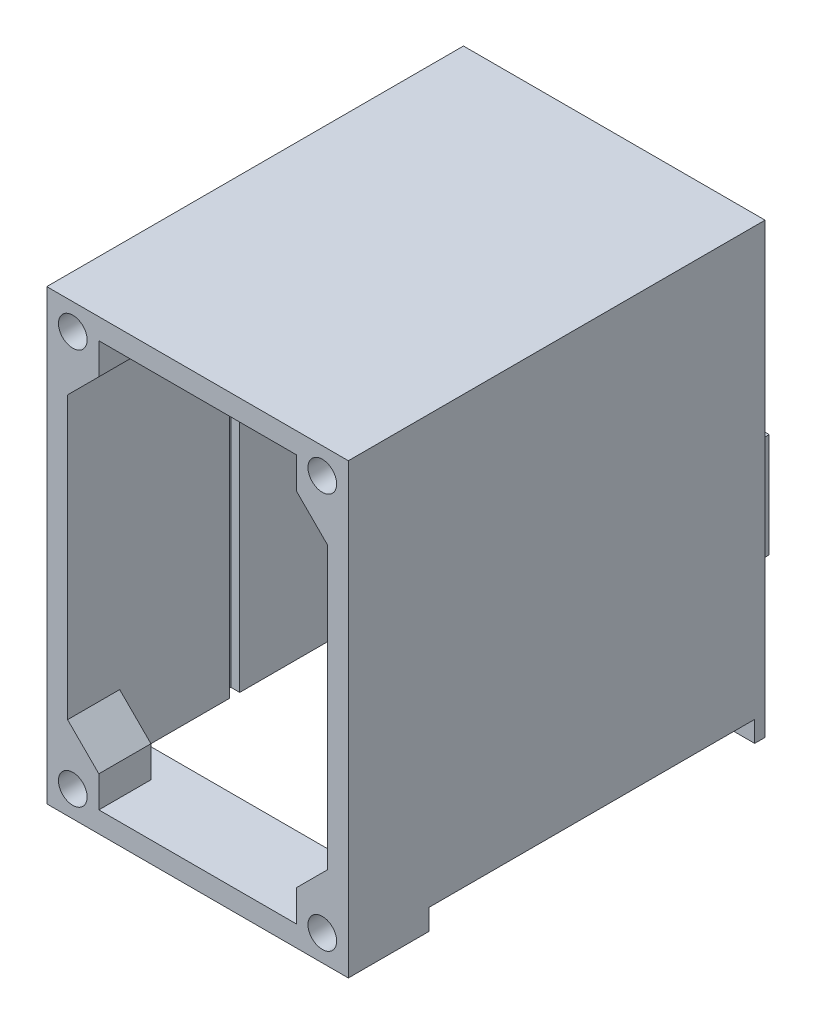
SolidWorks part; units mm, degrees
ref_plane "Plan de face" through (0, 0, 0) normal (0, 0, 1) x (1, 0, 0)
ref_plane "Plan de dessus" through (0, 0, 0) normal (0, 1, 0) x (1, 0, 0)
ref_plane "Plan de droite" through (0, 0, 0) normal (1, 0, 0) x (0, 0, -1)
sketch "Esquisse1" plane through (0, 0, 0) normal (0, 0, 1) x (1, 0, 0)
  line L1 (-28.95, 43) -> (28.95, 43)
  line L2 (-28.95, 43) -> (-28.95, -43)
  line L3 (-28.95, -43) -> (28.95, -43)
  line L4 (28.95, 43) -> (28.95, -43)
  line L5 (-28.95, 43) -> (28.95, -43) construction
  line L6 (-28.95, -43) -> (28.95, 43) construction
  point P0 (0, 0)
  dimension "D1" = 86
  dimension "D2" = 57.9
extrude "Boss.-Extru.1" add sketch "Esquisse1" along normal blind 80
sketch "Esquisse2" plane through (0, 0, 80) normal (0, 0, 1) x (1, 0, 0)
  line L0 (-28.95, 43) -> (-28.95, -43) construction
  line L1 (-24.95, 39) -> (24.95, 39)
  line L2 (-24.95, 39) -> (-24.95, -39)
  line L3 (-24.95, -39) -> (24.95, -39)
  line L4 (24.95, 39) -> (24.95, -39)
  line L5 (-24.95, 39) -> (24.95, -39) construction
  line L6 (-24.95, -39) -> (24.95, 39) construction
  line L7 (-28.95, -43) -> (28.95, -43) construction
  point P0 (0, 0)
  dimension "D1" = 4
  dimension "D2" = 4
extrude "Enlèv. mat.-Extru.1" cut sketch "Esquisse2" against normal blind 75 contours L3 L4 L1 L2
sketch "Esquisse3" plane through (0, 0, 80) normal (0, 0, 1) x (1, 0, 0)
  line L0 (28.95, 43) -> (-28.95, 43) construction
  line L1 (-28.95, 43) -> (-18.95, 43)
  line L2 (-28.95, 43) -> (-28.95, 33)
  line L3 (-28.95, 33) -> (-18.95, 33)
  line L4 (-18.95, 43) -> (-18.95, 33)
  line L5 (-28.95, -43) -> (-18.95, -43)
  line L6 (-28.95, -43) -> (-28.95, -33)
  line L7 (-28.95, -33) -> (-18.95, -33)
  line L8 (-18.95, -43) -> (-18.95, -33)
  line L9 (28.95, -43) -> (18.95, -43)
  line L10 (28.95, -43) -> (28.95, -33)
  line L11 (28.95, -33) -> (18.95, -33)
  line L12 (18.95, -43) -> (18.95, -33)
  line L13 (28.95, 43) -> (18.95, 43)
  line L14 (28.95, 43) -> (28.95, 33)
  line L15 (28.95, 33) -> (18.95, 33)
  line L16 (18.95, 43) -> (18.95, 33)
  line L17 (28.95, -43) -> (28.95, 43) construction
  dimension "D1" = 10
  dimension "D2" = 10
  dimension "D3" = 10
  dimension "D4" = 10
  dimension "D5" = 10
  dimension "D6" = 10
  dimension "D7" = 10
  dimension "D8" = 10
extrude "Boss.-Extru.2" add sketch "Esquisse3" against normal blind 10
sketch "Esquisse4" plane through (0, 0, 80) normal (0, 0, 1) x (1, 0, 0)
  line L0 (-18.95, 33) -> (-28.95, 43) construction
  line L2 (-28.95, -43) -> (28.95, -43) construction
  line L3 (-28.95, -43) -> (-18.95, -33) construction
  line L4 (28.95, 43) -> (-28.95, 43) construction
  line L6 (28.95, -43) -> (18.95, -33) construction
  line L7 (18.95, -33) -> (18.95, -39) construction
  line L8 (28.95, -43) -> (28.95, 43) construction
  circle A2 centre (23.95, -38) radius 2.75
  circle A5 centre (-23.95, -38) radius 2.75
  circle A6 centre (-23.95, 38) radius 2.75
  circle A7 centre (23.95, 38) radius 2.75
  dimension "D1" = 5.5
  dimension "D2" = 5
  dimension "D3" = 5.5
  dimension "D4" = 5.5
  dimension "D5" = 5.5
  dimension "D6" = 5
  dimension "D7" = 5
extrude "Enlèv. mat.-Extru.2" cut sketch "Esquisse4" against normal blind 5.85
sketch "Esquisse47" plane through (0, 0, 80) normal (0, 0, 1) x (1, 0, 0)
  circle A0 centre (23.95, 38) radius 2.75 construction
  circle A1 centre (-23.95, 38) radius 2.75 construction
  circle A2 centre (-23.95, -38) radius 2.75 construction
  circle A3 centre (23.95, -38) radius 2.75 construction
  circle A4 centre (23.95, 38) radius 2.75 construction
  circle A5 centre (-23.95, 38) radius 2.75 construction
  circle A6 centre (-23.95, -38) radius 2.75 construction
  circle A7 centre (23.95, -38) radius 2.75 construction
  circle A8 centre (23.95, -38) radius 2.25
  circle A9 centre (-23.95, -38) radius 2.25
  circle A10 centre (-23.95, 38) radius 2.25
  circle A11 centre (23.95, 38) radius 2.25
  dimension "D1" = 4.5
extrude "Enlèv. mat.-Extru.25" cut sketch "Esquisse47" against normal up to surface (10 mm away) up to face at (-21.95, 36, 70)
ref_plane "Plan1" through (-18.95, 33, 70) normal (0, 0, 1) x (1, 0, 0)
sketch "Esquisse19" plane through (0, 0, 0) normal (0, 0, -1) x (-1, 0, 0)
  line L0 (-28.95, 43) -> (28.95, 43) construction
  line L1 (25, -17) -> (-25, -17)
  line L2 (25, -17) -> (25, 3)
  line L3 (25, 3) -> (-25, 3)
  line L4 (-25, -17) -> (-25, 3)
  line L5 (25, -17) -> (-25, 3) construction
  line L6 (0, 0) -> (0, -7) construction
  dimension "D1" = 50
  dimension "D2" = 20
  dimension "D3" = 40
extrude "Boss.-Extru.9" add sketch "Esquisse19" along normal blind 4.75
sketch "Esquisse20" plane through (0, 3, 0) normal (0, 1, 0) x (1, 0, 0)
  line L0 (25, 4.75) -> (25, 0) construction
  line L1 (-25, 4.75) -> (25, 4.75)
  line L2 (-25, 4.75) -> (-25, 0)
  line L3 (-25, 0) -> (25, 0)
  line L4 (25, 4.75) -> (25, 0)
  dimension "D1" = 4.75
fillet "Congé1" radius 3 1 edges at (0, -17, 0)
sketch "Esquisse29" plane through (0, 0, -4.75) normal (0, 0, -1) x (-1, 0, 0)
  line L0 (0, 0) -> (0, -5) construction
  line L1 (5, -7.5) -> (-5, -7.5)
  line L2 (5, -7.5) -> (5, -2.5)
  line L3 (5, -2.5) -> (-5, -2.5)
  line L4 (-5, -7.5) -> (-5, -2.5)
  line L5 (5, -7.5) -> (-5, -2.5) construction
  line L6 (5, -2.5) -> (-5, -7.5) construction
  point P0 (0, -5)
  dimension "D1" = 5
  dimension "D2" = 5
  dimension "D3" = 10
extrude "Enlèv. mat.-Extru.11" cut sketch "Esquisse29" against normal through all
sketch "Esquisse32" plane through (0, -43, 0) normal (0, -1, 0) x (1, 0, 0)
  line L7 (-28.95, 80) -> (-28.95, 0) construction
  line L9 (-26.6919, 32.4657) -> (-26.6919, 30.7657)
  line L11 (28.3081, 32.4657) -> (28.3081, 30.7657)
  line L12 (-28.95, 64.5) -> (28.95, 64.5)
  line L13 (-28.95, 64.5) -> (-28.95, 2)
  line L14 (-28.95, 2) -> (28.95, 2)
  line L15 (28.95, 64.5) -> (28.95, 2)
  line L16 (28.95, 80) -> (28.95, 0) construction
  line L17 (-25, 0) -> (25, 0) construction
  dimension "D1" = 0
  dimension "D2" = 0
  dimension "D3" = 2
  dimension "D4" = 62.5
extrude "Enlèv. mat.-Extru.16" cut sketch "Esquisse32" against normal blind 4 contours L15 L14 L13 L12
sketch "Esquisse46" plane through (0, -39, 0) normal (0, -1, 0) x (1, 0, 0)
  line L0 (-24.95, 5) -> (24.95, 5) construction
  line L1 (-24.95, 13) -> (-21.95, 13)
  line L2 (-24.95, 13) -> (-24.95, 18.5)
  line L3 (-24.95, 18.5) -> (-21.95, 18.5)
  line L4 (-21.95, 13) -> (-21.95, 18.5)
  line L5 (-24.95, 5) -> (-24.95, 64.5) construction
  dimension "D1" = 8
  dimension "D2" = 5.5
  dimension "D3" = 3
extrude "Boss.-Extru.10" add sketch "Esquisse46" against normal up to surface (78 mm away) up to face at (0, 39, 59)
sketch "Esquisse38" plane through (-24.95, 0, 0) normal (1, 0, 0) x (0, 0, -1)
  line L0 (-15.975, -39) -> (-15.975, 36) construction
  line L1 (-16.95, -39) -> (-16.95, 36)
  line L2 (-15, -39) -> (-15, 36)
  line L3 (-5, 39) -> (-5, -39) construction
  line L4 (-64.5, -39) -> (-70, -39) construction
  arc A0 (-16.95, -39) -> (-15, -39) centre (-15.975, -39) ccw
  arc A1 (-15, 36) -> (-16.95, 36) centre (-15.975, 36) ccw
  point P2 (-15.975, -1.5)
  dimension "D1" = 10
  dimension "D4" = 1.95
  dimension "D5" = 0
  dimension "D2" = 10
  dimension "D3" = 75
extrude "Enlèv. mat.-Extru.20" cut sketch "Esquisse38" against normal blind 1.5 and the other way blind 10
sketch "Esquisse40" plane through (-24.95, 0, 0) normal (1, 0, 0) x (0, 0, -1)
  line L0 (-47.925, 36) -> (-47.925, -39) construction
  line L1 (-46.95, 36) -> (-46.95, -39)
  line L2 (-48.9, 36) -> (-48.9, -39)
  line L4 (-64.5, -39) -> (-70, -39) construction
  line L5 (-16.95, -39) -> (-16.95, 36) construction
  arc A0 (-46.95, 36) -> (-48.9, 36) centre (-47.925, 36) ccw
  arc A1 (-48.9, -39) -> (-46.95, -39) centre (-47.925, -39) ccw
  point P2 (-47.925, -1.5)
  dimension "D1" = 30
  dimension "D2" = 1.95
  dimension "D3" = 75
  dimension "D4" = 0
extrude "Enlèv. mat.-Extru.21" cut sketch "Esquisse40" against normal blind 1.7 contours L2 A1 L1 A0
chamfer "Chanfrein1" distance 6 angle 45 4 edges at (24.95, -33, 75) (-24.95, -33, 75) (24.95, 33, 75) (-24.95, 33, 75)
sketch "Esquisse42" plane through (0, 0, 74.15) normal (0, 0, 1) x (1, 0, 0)
ref_plane "Plan7" through (0, 0, 0) normal (1, 0, 0) x (0, 0, -1)
mirror "Symétrie1" about plane through (0, 0, 0) normal (1, 0, 0) of "Boss.-Extru.10", "Enlèv. mat.-Extru.20", "Enlèv. mat.-Extru.21"
sketch "Esquisse45" plane through (0, 0, -4.75) normal (0, 0, -1) x (-1, 0, 0)
  line L0 (-25, 3) -> (-25, -20) construction
  line L3 (-25, -17) -> (25, -17) construction
  circle A0 centre (17, -6) radius 2.75
  circle A1 centre (-17, -6) radius 2.75
  dimension "D1" = 5.5
  dimension "D2" = 5.5
  dimension "D3" = 34
  dimension "D4" = 8
  dimension "D5" = 11
  dimension "D6" = 11
extrude "Enlèv. mat.-Extru.24" cut sketch "Esquisse45" against normal through all
sketch "Esquisse8" plane through (0, 0, 5) normal (0, 0, 1) x (1, 0, 0)
sketch "Esquisse48" plane through (0, -39, 0) normal (0, -1, 0) x (1, 0, 0)
  line L0 (0, 7) -> (0, 0) construction
  line L1 (-4, 9) -> (4, 9)
  line L2 (-4, 9) -> (-4, 5)
  line L3 (-4, 5) -> (4, 5)
  line L4 (4, 9) -> (4, 5)
  line L5 (-4, 9) -> (4, 5) construction
  line L6 (-4, 5) -> (4, 9) construction
  line L7 (-24.95, 5) -> (24.95, 5) construction
  point P0 (0, 7)
  dimension "D1" = 4
  dimension "D2" = 8
extrude "Boss.-Extru.11" add sketch "Esquisse48" against normal blind 15
sketch "Esquisse49" plane through (0, -39, 0) normal (0, -1, 0) x (1, 0, 0)
  line L0 (0, 9) -> (0, 5.5) construction
  line L1 (4, 9) -> (-4, 9) construction
  circle A0 centre (0, 5.5) radius 2.75
  dimension "D1" = 5.5
  dimension "D2" = 3.5
extrude "Enlèv. mat.-Extru.26" cut sketch "Esquisse49" against normal blind 15
fillet "Congé2" radius 2 4 edges at (4, -31.5, 5) (4, -31.5, 9) (-4, -31.5, 9) (-4, -31.5, 5)
